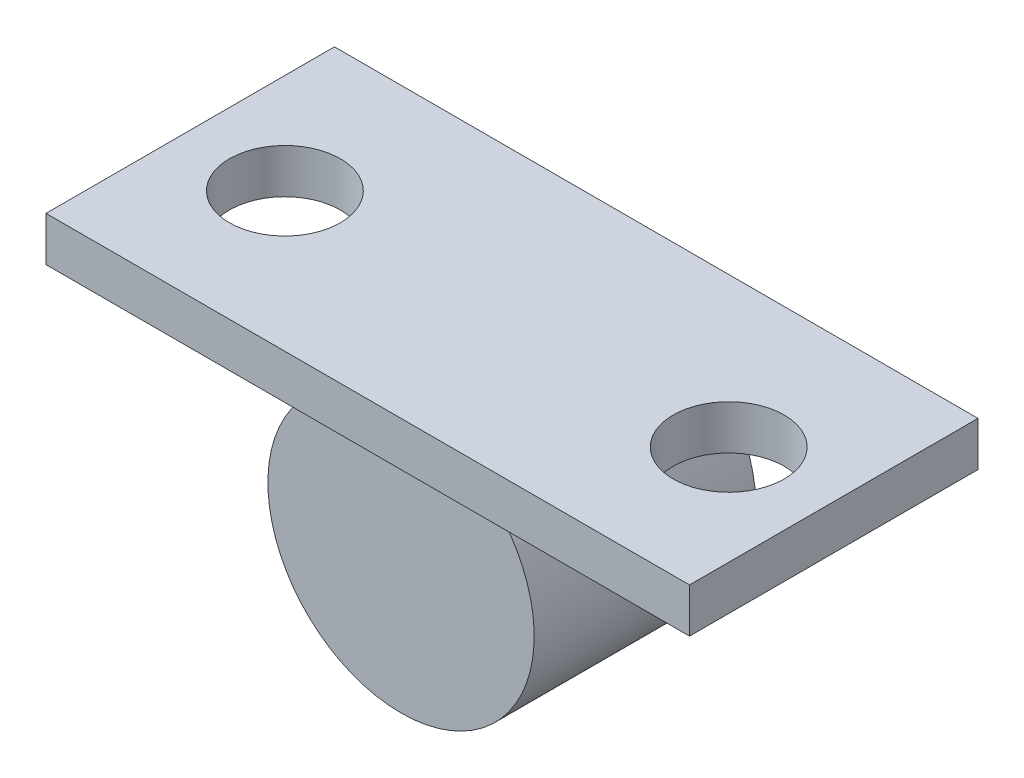
SolidWorks part; units mm, degrees
ref_plane "前视基准面" through (0, 0, 0) normal (0, 0, 1) x (1, 0, 0)
ref_plane "上视基准面" through (0, 0, 0) normal (0, 1, 0) x (1, 0, 0)
ref_plane "右视基准面" through (0, 0, 0) normal (1, 0, 0) x (0, 0, -1)
other "Configuration Table"
sketch "草图1" plane through (0, 0, 0) normal (0, 1, 0) x (1, 0, 0)
  line L1 (-14.5, 6.5) -> (14.5, 6.5)
  line L2 (-14.5, 6.5) -> (-14.5, -6.5)
  line L3 (-14.5, -6.5) -> (14.5, -6.5)
  line L4 (14.5, 6.5) -> (14.5, -6.5)
  line L5 (-14.5, 6.5) -> (14.5, -6.5) construction
  line L6 (-14.5, -6.5) -> (14.5, 6.5) construction
  point P0 (0, 0)
  dimension "D1" = 29
  dimension "D2" = 13
extrude "凸台-拉伸1" add sketch "草图1" against normal blind 2
sketch "草图2" plane through (0, 0, 0) normal (0, 1, 0) x (1, 0, 0)
  line L0 (0, 0) -> (0, 6.5) construction
  line L1 (14.5, 6.5) -> (-14.5, 6.5) construction
  circle A0 centre (-10, -0.235) radius 2.5
  circle A1 centre (10, -0.235) radius 2.5
  dimension "D1" = 5
  dimension "D2" = 20
extrude "切除-拉伸1" cut sketch "草图2" against normal through all
sketch "草图3" plane through (0, 0, 0) normal (0, 0, 1) x (1, 0, 0)
  line L1 (-14.5, 0) -> (14.5, 0) construction
  circle A1 centre (0, -7) radius 6
  dimension "D1" = 13
  dimension "D2" = 7
extrude "凸台-拉伸2" add sketch "草图3" along normal mid plane 10
ref_axis "基准轴1" through (0, -13.65, 0) along (0, 1, 0)
